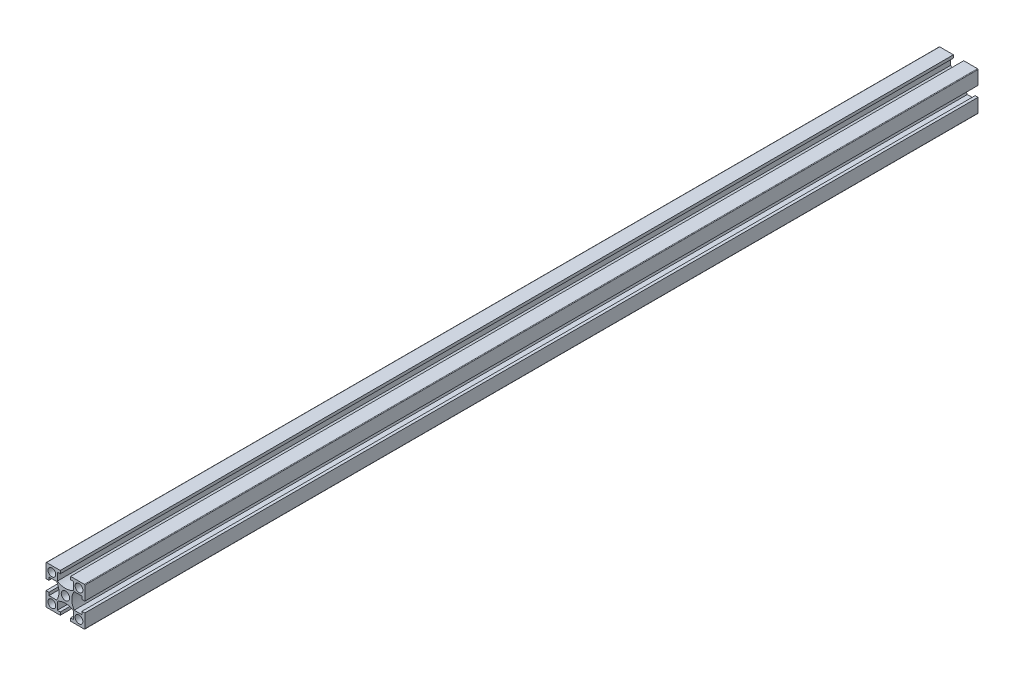
SolidWorks part; units mm, degrees
material "3.0255 (EN-AW 1350A)"
ref_plane "정면" through (0, 0, 0) normal (0, 0, 1) x (1, 0, 0)
ref_plane "윗면" through (0, 0, 0) normal (0, 1, 0) x (1, 0, 0)
ref_plane "우측면" through (0, 0, 0) normal (1, 0, 0) x (0, 0, -1)
sketch "스케치1" plane through (0, 0, 0) normal (0, 0, 1) x (1, 0, 0)
  line L0 (0, 32.0265) -> (0, -31.6588) construction
  line L1 (-10, 10) -> (-10, -10)
  line L2 (-10, 10) -> (10, 10)
  line L3 (-10, 2.65) -> (-8.5, 2.65)
  line L4 (13.6618, 0) -> (-11.6993, 0) construction
  line L5 (-8.5, 2.65) -> (-8.5, 4.15)
  line L6 (-8.5, 4.15) -> (-4.5032, 4.15)
  line L7 (-10, -2.65) -> (-8.5, -2.65)
  line L8 (-8.5, -2.65) -> (-8.5, -4.15)
  line L9 (-8.5, -4.15) -> (-4.5032, -4.15)
  line L10 (-10, -10) -> (10, -10)
  line L11 (10, 10) -> (10, -10)
  circle A0 centre (-7, 7) radius 2
  circle A1 centre (-7, -7) radius 2
  arc A2 (-4.5032, 4.15) -> (-4.5032, -4.15) centre (-11.0587, 0) cw
  circle A3 centre (0, 0) radius 2.15
  circle A4 centre (7, 7) radius 2
  circle A5 centre (7, -7) radius 2
  point P21 (-10, 0)
  point P23 (-3.3, 0)
  point P31 (0, -10)
  point P32 (0, 10)
  dimension "D3" = 4
  dimension "D9" = 6.7
  dimension "D10" = 4.3
  dimension "D11" = 7.7587
  dimension "D1" = 20
  dimension "D2" = 20
  dimension "D4" = 14
  dimension "D5" = 14
  dimension "D6" = 5.3
  dimension "D7" = 8.3
  dimension "D8" = 1.5
extrude "보스-돌출1" add sketch "스케치1" along normal blind 460 contours A0 | A4 | A3 | A5 | A1 | A2 L6 L5 L3 L1 L7 L8 L9 | L2 L11 L10 L1 region at (-6.6069, 0, 0) region at (-7, 7, 0) region at (-7, -7, 0) region at (0, 0, 0) region at (7, 7, 0) region at (7, -7, 0)
extrude "컷-돌출1" cut sketch "스케치1<3>" along normal up to next contours A2 L6 L5 L3 L1 L7 L8 L9 region at (-6.6069, 0, 0)
sketch "스케치1<3>" plane through (0, 0, 0) normal (0, 0, 1) x (1, 0, 0) same geometry as "스케치1"
pattern_circular "원형 패턴1" count 4 over 360 about axis through (0, 0, 460) along (0, 0, -1) of "컷-돌출1" reverse direction yes
fillet "필렛1" radius 0.3 4 edges at (10, -10, 230) (-10, -10, 230) (-10, 10, 230) (10, 10, 230)
sketch "스케치2" plane through (-10, 0, 0) normal (-1, 0, 0) x (0, 0, 1)
  line L0 (0, 4.15) -> (0, -4.15) construction
  line L1 (460, -4.15) -> (460, 4.15) construction
  circle A0 centre (31, 0) radius 2.5
  circle A1 centre (429, 0) radius 2.5
  dimension "D1" = 31
  dimension "D2" = 31
extrude "컷-돌출2" cut sketch "스케치2" against normal through all
sketch "스케치3" plane through (0, 10, 0) normal (0, 1, 0) x (1, 0, 0)
  line L0 (4.15, 0) -> (-4.15, 0) construction
  line L1 (-4.15, -460) -> (4.15, -460) construction
  circle A0 centre (0, -10) radius 2.15
  circle A1 centre (0, -450) radius 2.15
  dimension "D1" = 10
  dimension "D2" = 10
  dimension "D3" = 4.3
  dimension "D4" = 4.3
extrude "컷-돌출3" cut sketch "스케치3" against normal through all
sketch "스케치4" plane through (-10, 0, 0) normal (-1, 0, 0) x (0, 0, 1)
  line L0 (460, -2.65) -> (460, -9.7) construction
  line L1 (460, -4.15) -> (460, 4.15) construction
  line L2 (0, 4.15) -> (0, -4.15) construction
  circle A0 centre (10, 0) radius 2.15
  circle A1 centre (450, 0) radius 2.15
  circle A2 centre (270, 0) radius 2.5
  circle A3 centre (190, 0) radius 2.5
  dimension "D1" = 4.3
  dimension "D4" = 190
  dimension "D5" = 190
  dimension "D2" = 10
  dimension "D3" = 10
extrude "컷-돌출4" cut sketch "스케치4" against normal through all
